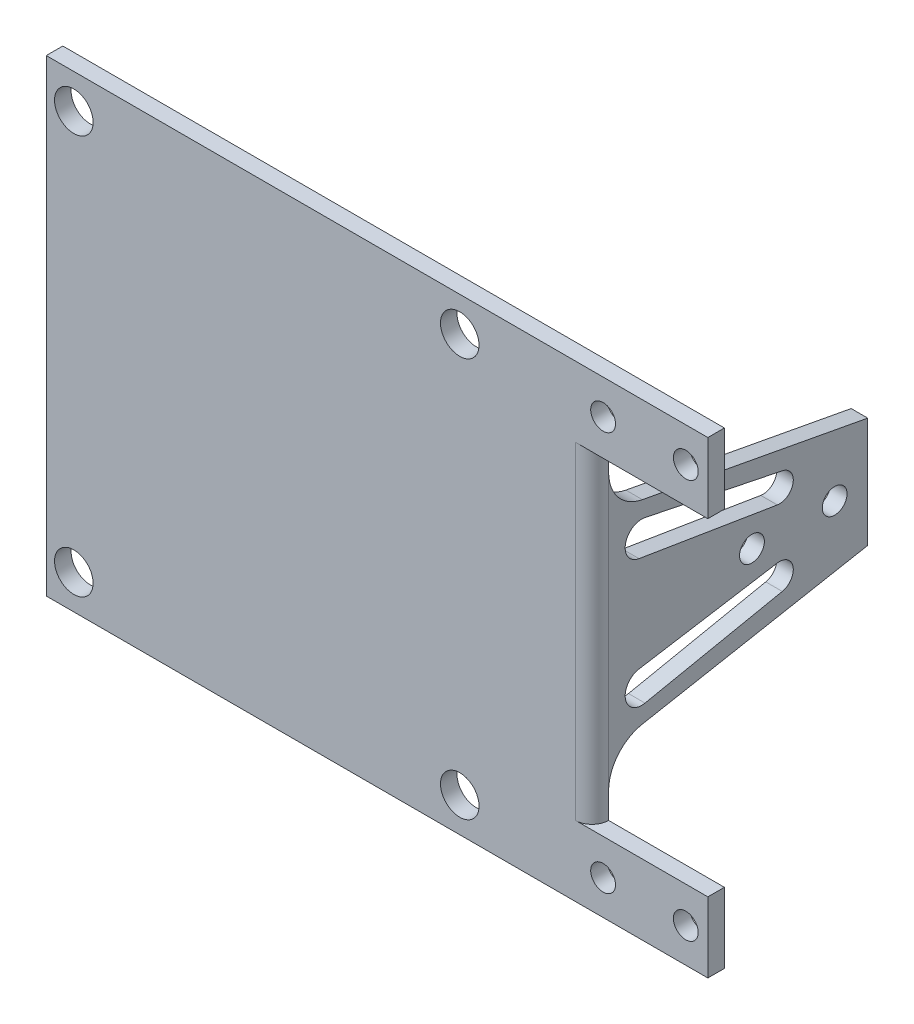
SolidWorks part; units mm, degrees
ref_plane "Front Plane" through (0, 0, 0) normal (0, 0, 1) x (1, 0, 0)
ref_plane "Top Plane" through (0, 0, 0) normal (0, 1, 0) x (1, 0, 0)
ref_plane "Right Plane" through (0, 0, 0) normal (1, 0, 0) x (0, 0, -1)
sketch "Sketch1" plane through (0, 0, 0) normal (0, 0, 1) x (1, 0, 0)
  line L0 (120, 29.7) -> (96, 29.7)
  line L1 (0, 0) -> (76, 0) construction
  line L2 (0, -42.45) -> (0, 42.45)
  line L3 (0, 42.45) -> (120, 42.45)
  line L4 (120, 29.7) -> (120, 42.45)
  line L9 (96, 0) -> (0, 0)
  line L13 (20, 36.2) -> (38.9382, 36.2) construction
  line L14 (96, 29.7) -> (96, -29.7)
  line L15 (0, 0) -> (96, 0)
  line L16 (20, -36.2) -> (38.9382, -36.2) construction
  line L17 (120, -29.7) -> (120, -42.45)
  line L18 (0, -42.45) -> (120, -42.45)
  line L19 (120, -29.7) -> (96, -29.7)
  circle A1 centre (5, 36.2) radius 3.5
  circle A2 centre (75, 36.2) radius 3.5
  circle A3 centre (5, -36.2) radius 3.5
  circle A4 centre (75, -36.2) radius 3.5
  circle A5 centre (116, 36.2) radius 2.25
  circle A6 centre (101, 36.2) radius 2.25
  circle A7 centre (101, -36.2) radius 2.25
  circle A8 centre (116, -36.2) radius 2.25
  dimension "D5" = 4
  dimension "D6" = 12.75
  dimension "D8" = 7
  dimension "D10" = 7
  dimension "D7" = 4.5
  dimension "D12" = 4.5
  dimension "D1" = 120
  dimension "D2" = 6.25
  dimension "D3" = 36.2
  dimension "D4" = 96
  dimension "D9" = 5
  dimension "D11" = 70
  dimension "D13" = 15
extrude "Boss-Extrude1" add sketch "Sketch1" against normal blind 3 contours L2 L4 L3 | L17 L19 L14 L9 L2 L18 region at (51.991, 21.9073, 0) region at (51.991, -21.9073, 0)
sketch "Sketch3" plane through (96, 0, 0) normal (1, 0, 0) x (0, 0, -1)
  line L0 (0, 0) -> (90.3797, 0) construction
  line L1 (0, 29.7) -> (3, 29.7)
  line L2 (50, -10) -> (50, 10)
  line L3 (3, 29.7) -> (3, -29.7) construction
  line L4 (0, -29.7) -> (3, -29.7)
  line L5 (50, 10) -> (9.1243, 17.6273)
  line L6 (3, 29.7) -> (3, 25)
  line L7 (0, 29.7) -> (0, -29.7)
  line L8 (0, 29.7) -> (0, -29.7) construction
  line L10 (3, -29.7) -> (3, 25)
  line L11 (50, -10) -> (9.1243, -17.6273)
  line L12 (8.5153, -8.6667) -> (33.596, -4.5601)
  line L13 (9.6008, 14.5665) -> (34.5007, 9.4766)
  line L14 (8.5153, 8.6667) -> (33.596, 4.5601)
  line L15 (9.6008, -14.5665) -> (34.5007, -9.4766)
  arc A0 (3, 25) -> (9.1243, 17.6273) centre (10.5, 25) ccw
  arc A1 (3, -25) -> (9.1243, -17.6273) centre (10.5, -25) cw
  arc A2 (9.6008, 14.5665) -> (8.5153, 8.6667) centre (9, 11.6273) ccw
  arc A3 (33.596, 4.5601) -> (34.5007, 9.4766) centre (34, 7.0273) ccw
  arc A4 (9.6008, -14.5665) -> (8.5153, -8.6667) centre (9, -11.6273) cw
  arc A5 (33.596, -4.5601) -> (34.5007, -9.4766) centre (34, -7.0273) cw
  circle A6 centre (44, 0) radius 2.25
  circle A7 centre (29, 0) radius 2.25
  point P23 (50, 0)
  line M3 (3, -29.7) -> (3, 29.7)
  dimension "D2" = 15
  dimension "D7" = 6
  dimension "D8" = 5
  dimension "D11" = 4.5
  dimension "D12" = 4.5
  dimension "D1" = 50
  dimension "D3" = 10
  dimension "D4" = 25
  dimension "D5" = 6
  dimension "D6" = 6
  dimension "D9" = 4.6
  dimension "D10" = 25
  dimension "D13" = 6
  dimension "D14" = 15
extrude "Boss-Extrude2" add sketch "Sketch3" along normal blind 3 contours L0 L2 L5 A0 M3 | L0 L10 A1 L11 L2 | L6 L1 L7 L4 L10 region at (96, 0, -24.4935)
fillet "Fillet1" radius 3 1 edges at (99, 0, 0)
fillet "Fillet2" radius 3 1 edges at (96, 0, -3)
